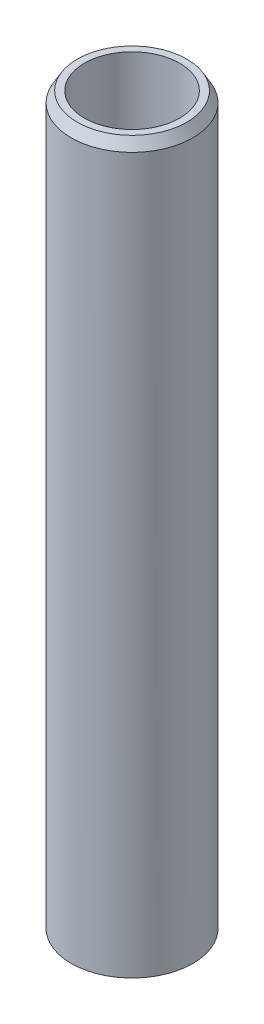
SolidWorks part; units mm, degrees
ref_plane "Front Plane" through (0, 0, 0) normal (0, 0, 1) x (1, 0, 0)
ref_plane "Top Plane" through (0, 0, 0) normal (0, 1, 0) x (1, 0, 0)
ref_plane "Right Plane" through (0, 0, 0) normal (1, 0, 0) x (0, 0, -1)
sketch "Sketch1" plane through (0, 0, 0) normal (0, 1, 0) x (1, 0, 0)
  circle A0 centre (0, 0) radius 25
  dimension "SHAFT_OD" = 50
extrude "Boss-Extrude1" add sketch "Sketch1" along normal blind 300.749
sketch "Sketch2" plane through (0, 0, 0) normal (0, 1, 0) x (1, 0, 0)
  circle A0 centre (0, 0) radius 19.5843
  dimension "BORE_D" = 39.1685
extrude "Cut-Extrude1" cut sketch "Sketch2" along normal through all
chamfer "Chamfer1" distance 4.3142 angle 30 2 edges at (0, 300.749, 25) (0, 0, 25) first distance on face at (0, 300.749, 25) first distance on face at (0, 0, 19.5843)
